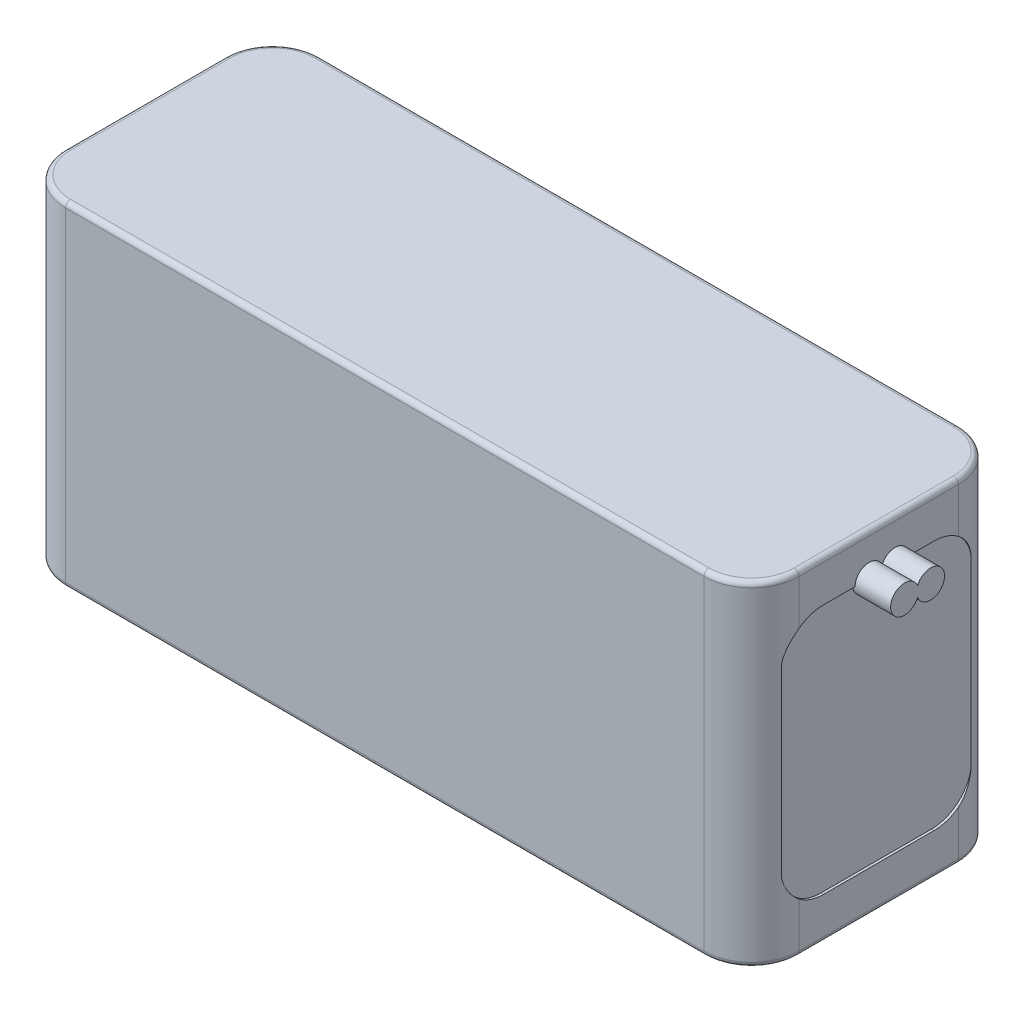
SolidWorks part; units mm, degrees
ref_plane "Front Plane" through (0, 0, 0) normal (0, 0, 1) x (1, 0, 0)
ref_plane "Top Plane" through (0, 0, 0) normal (0, 1, 0) x (1, 0, 0)
ref_plane "Right Plane" through (0, 0, 0) normal (1, 0, 0) x (0, 0, -1)
ref_plane "Plane1" through (0, 0, -15) normal (0, 0, -1) x (-1, 0, 0)
sketch "Sketch1" plane through (0, 0, -15) normal (0, 0, -1) x (-1, 0, 0)
  line L0 (-69, -22) -> (78, -22)
  line L1 (78, -22) -> (78, 45)
  line L2 (78, 45) -> (-69, 45)
  line L3 (-69, 45) -> (-69, -22)
  line L4 (-69, 11.5) -> (78, 11.5) construction
  line L5 (4.5, 45) -> (4.5, -22) construction
  dimension "D1" = 67
  dimension "D2" = 147
extrude "Boss-Extrude1" add sketch "Sketch1" against normal blind 51
sketch "Sketch2" plane through (69, 0, 0) normal (1, 0, 0) x (0, 0, -1)
  line L0 (-29.625, 28.625) -> (-29.625, -5.625)
  line L1 (-21.625, -13.625) -> (0.625, -13.625)
  line L2 (8.625, -5.625) -> (8.625, 28.625)
  line L3 (0.625, 36.625) -> (-21.625, 36.625)
  line L4 (-36, 45) -> (15, -22) construction
  line L5 (15, 45) -> (-36, -22) construction
  line L6 (-29.625, 36.625) -> (8.625, -13.625) construction
  line L7 (8.625, 36.625) -> (-29.625, -13.625) construction
  line L12 (-36, 45) -> (15, 45) construction
  line L13 (-36, 45) -> (-36, -22) construction
  line L14 (-36, -22) -> (15, -22) construction
  line L15 (15, 45) -> (15, -22) construction
  line L16 (-36, 45) -> (15, -22) construction
  line L17 (-36, -22) -> (15, 45) construction
  arc A0 (-29.625, -5.625) -> (-21.625, -13.625) centre (-21.625, -5.625) ccw
  arc A1 (0.625, -13.625) -> (8.625, -5.625) centre (0.625, -5.625) ccw
  arc A2 (8.625, 28.625) -> (0.625, 36.625) centre (0.625, 28.625) ccw
  arc A3 (-29.625, 28.625) -> (-21.625, 36.625) centre (-21.625, 28.625) cw
  point P16 (-10.5, 11.5)
  dimension "D3" = 8
  dimension "D1" = 38.25
  dimension "D2" = 51
extrude "Cut-Extrude1" cut sketch "Sketch2" against normal blind 0.5
sketch "Sketch3" plane through (-78, 0, 0) normal (-1, 0, 0) x (0, 0, 1)
  line L0 (18.195, 36.625) -> (2.805, 36.625)
  line L1 (-8.625, 25.195) -> (-8.625, -2.195)
  line L2 (2.805, -13.625) -> (18.195, -13.625)
  line L3 (29.625, -2.195) -> (29.625, 25.195)
  line L4 (-8.625, 36.625) -> (29.625, -13.625) construction
  line L5 (29.625, 36.625) -> (-8.625, -13.625) construction
  line L6 (-15, 45) -> (36, -22) construction
  line L7 (36, -22) -> (-15, -22) construction
  line L8 (-15, -22) -> (36, 45) construction
  arc A0 (-8.625, -2.195) -> (2.805, -13.625) centre (2.805, -2.195) ccw
  arc A1 (18.195, -13.625) -> (29.625, -2.195) centre (18.195, -2.195) ccw
  arc A2 (18.195, 36.625) -> (29.625, 25.195) centre (18.195, 25.195) cw
  arc A3 (2.805, 36.625) -> (-8.625, 25.195) centre (2.805, 25.195) ccw
  dimension "D3" = 11.43
  dimension "D1" = 38.25
  dimension "D2" = 51
extrude "Cut-Extrude2" cut sketch "Sketch3" against normal blind 0.5
fillet "Fillet1" radius 9.525 4 edges at (-78, 11.5, -15) (-78, 11.5, 36) (69, 11.5, -15) (69, 11.5, 36) tangent propagation no
fillet "Fillet2" radius 1 16 edges at (66.2102, 45, -12.2102) (69, 45, 10.5) (-4.5, 45, -15) (66.2102, 45, 33.2102) (-75.2102, 45, -12.2102) (-4.5, 45, 36) (-78, 45, 10.5) (-75.2102, 45, 33.2102) (-78, -22, 10.5) (-75.2102, -22, -12.2102) (-75.2102, -22, 33.2102) (-4.5, -22, -15) (-4.5, -22, 36) (66.2102, -22, -12.2102) (66.2102, -22, 33.2102) (69, -22, 10.5) tangent propagation no
sketch "Sketch4" plane through (0, 0, 36) normal (0, 0, 1) x (1, 0, 0)
  line L0 (-68.475, 11.5) -> (59.475, 11.5) construction
  line L1 (-68.475, 44) -> (-68.475, -21) construction
  line L2 (59.475, -21) -> (59.475, 44) construction
  line L3 (-4.5, 25.9735) -> (-4.5, -21) construction
  line L4 (-68.475, -21) -> (59.475, -21) construction
  circle A0 centre (-4.5, 11.5) radius 0.5026
sketch "Sketch5" plane through (68.5, 0, 0) normal (1, 0, 0) x (0, 0, -1)
  line L0 (0.625, 36.625) -> (-21.625, 36.625) construction
  line L1 (0.625, 36.625) -> (-21.625, 36.625) construction
  circle A0 centre (-12.4391, 36.625) radius 2.794
  circle A1 centre (-7.2257, 36.625) radius 2.794
  point P4 (-12.4391, 36.625)
  point P7 (-7.2257, 36.625)
  line M4 (0.625, 36.625) -> (-21.625, 36.625)
  dimension "D1" = 5.588
extrude "Boss-Extrude2" add sketch "Sketch5" along normal blind 7.62 and the other way blind 2.54 contours A1 A0 M4 | A1 A0 M4 | A1 A0 M4 | A0 A1 M4 | A1 A0 M4 | A0 A1 M4 region at (68.5, 37.0039, 9.8324) region at (68.5, 35.4222, 7.1708) region at (68.5, 37.8278, 7.1708) region at (68.5, 36.2461, 9.8324) region at (68.5, 37.8278, 12.494) region at (68.5, 35.4222, 12.494)
equation "\"D1@Sketch3\"=\"D2@Sketch3\" * .75"
equation "\"D1@Sketch2\"=\"D2@Sketch2\"* .75"
